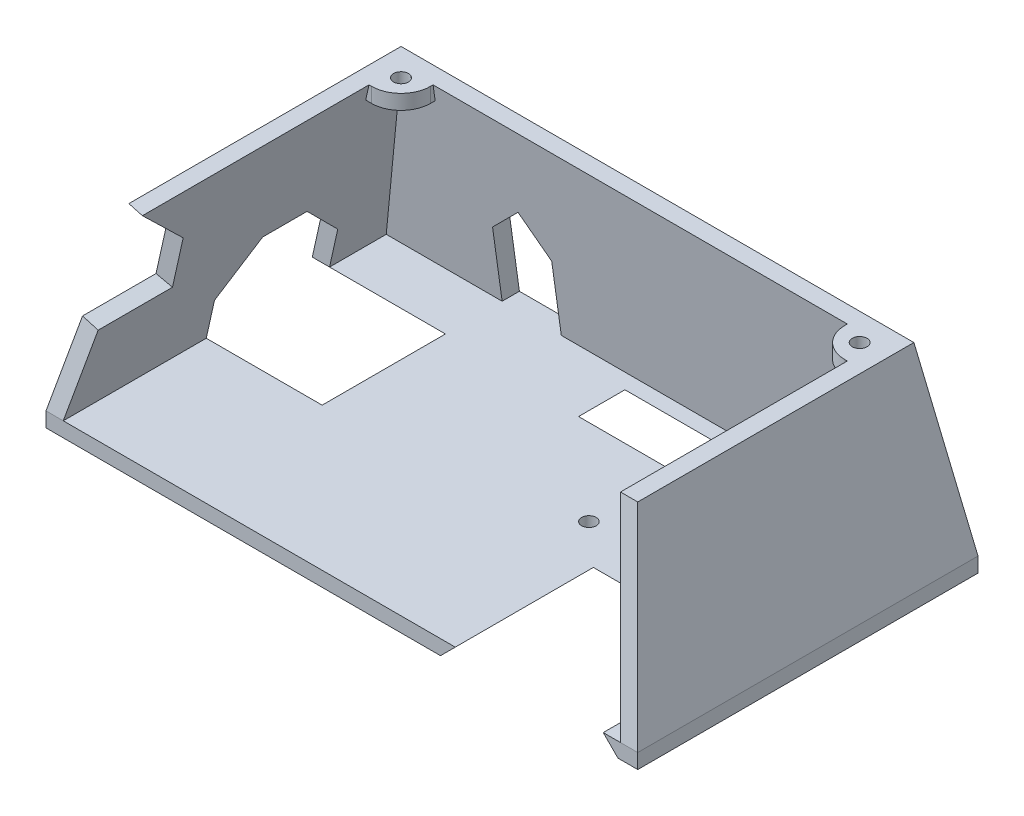
SolidWorks part; units mm, degrees
ref_plane "Front Plane" through (0, 0, 0) normal (0, 0, 1) x (1, 0, 0)
ref_plane "Top Plane" through (0, 0, 0) normal (0, 1, 0) x (1, 0, 0)
ref_plane "Right Plane" through (0, 0, 0) normal (1, 0, 0) x (0, 0, -1)
sketch "Sketch2" plane through (0, 0, 0) normal (0, 1, 0) x (1, 0, 0)
  line L0 (113, 0) -> (120, 0)
  line L1 (0, 0) -> (83, 0)
  line L2 (0, 0) -> (0, 69)
  line L3 (0, 69) -> (120, 69)
  line L4 (120, 0) -> (120, 69)
  line L5 (0, 0) -> (120, 69) construction
  line L6 (0, 69) -> (120, 0) construction
  line L7 (55, 62.4) -> (105, 62.4)
  line L8 (55, 62.4) -> (55, 53)
  line L9 (55, 53) -> (105, 53)
  line L10 (105, 62.4) -> (105, 53)
  line L11 (55, 62.4) -> (105, 53) construction
  line L12 (55, 53) -> (105, 62.4) construction
  line L13 (83, 28) -> (113, 28)
  line L14 (83, 28) -> (83, 0)
  line L16 (113, 28) -> (113, 0)
  line L17 (83, 28) -> (113, 0) construction
  line L18 (83, 0) -> (113, 28) construction
  point P18 (13.8909, 17.2356)
  dimension "D1" = 69
  dimension "D2" = 120
  dimension "D3" = 6.6
  dimension "D4" = 16
  dimension "D5" = 50
  dimension "D6" = 15
  dimension "D7" = 7
  dimension "D9" = 30
  dimension "D10" = 28
extrude "Boss-Extrude1" add sketch "Sketch2" along normal blind 3
sketch "Sketch3" plane through (0, 3, 0) normal (0, 1, 0) x (1, 0, 0)
  line L0 (3.5, 0) -> (3.5, 65.5)
  line L1 (3.5, 65.5) -> (116.5, 65.5)
  line L2 (116.5, 65.5) -> (116.5, 0)
  line L8 (0, 69) -> (0, 0)
  line L9 (0, 0) -> (83, 0)
  line L10 (83, 0) -> (83, 28)
  line L11 (83, 28) -> (113, 28)
  line L12 (113, 28) -> (113, 0)
  line L13 (113, 0) -> (120, 0)
  line L14 (120, 0) -> (120, 69)
  line L15 (120, 69) -> (0, 69)
  line L16 (0, 69) -> (0, 0)
  line L17 (0, 0) -> (3.5, 0)
  line L21 (116.5, 0) -> (120, 0)
  line L22 (120, 0) -> (120, 69)
  line L23 (120, 69) -> (0, 69)
  dimension "D2" = 3.5
  dimension "D3" = 3.5
  dimension "D4" = 3.5
  dimension "D1" = 0
ref_plane "Plane1" through (0, 39, 0) normal (0, 1, 0) x (1, 0, 0)
sketch "Sketch4" plane through (0, 39, 0) normal (0, 1, 0) x (1, 0, 0)
  line L0 (0, 73.6096) -> (8, 73.6096) construction
  line L1 (11.5, 8) -> (8, 8)
  line L2 (11.5, 8) -> (11.5, 60.5)
  line L4 (8, 8) -> (8, 64)
  line L5 (120, 32.6475) -> (112, 32.6475) construction
  line L6 (120, 0) -> (120, 69) construction
  line L7 (8, 64) -> (112, 64)
  line L11 (0, 69) -> (0, 0) construction
  line L14 (112, 64) -> (112, 8)
  line L15 (112, 8) -> (108.5, 8)
  line L17 (120, 69) -> (0, 69) construction
  line L22 (108.5, 60.5) -> (108.5, 8)
  line L27 (11.5, 60.5) -> (108.5, 60.5)
  point P4 (6.9167, 30.114)
  point P8 (54.6167, 56.9239)
  point P12 (99.6607, 30.8288)
  dimension "D1" = 3.5
  dimension "D2" = 3.5
  dimension "D3" = 3.5
  dimension "D4" = 56
  dimension "D5" = 104
  dimension "D6" = 5
loft "Loft1" add profiles "Sketch4", "Sketch3"
sketch "Sketch5" plane through (0, 39, 0) normal (0, 1, 0) x (1, 0, 0)
  line L0 (112, 64) -> (8, 64) construction
  line L1 (8, 64) -> (18, 64)
  line L2 (8, 64) -> (8, 54)
  line L3 (8, 54) -> (12, 54)
  line L4 (18, 64) -> (18, 60)
  line L5 (8, 64) -> (18, 54) construction
  line L6 (8, 54) -> (18, 64) construction
  line L7 (112, 64) -> (102, 64)
  line L8 (112, 64) -> (112, 54)
  line L9 (112, 54) -> (108, 54)
  line L10 (102, 64) -> (102, 60)
  line L11 (112, 64) -> (102, 54) construction
  line L12 (112, 54) -> (102, 64) construction
  line L13 (8, 64) -> (8, 8) construction
  line L14 (112, 8) -> (112, 64) construction
  arc A0 (108, 54) -> (102, 60) centre (108, 60) cw
  arc A1 (12, 54) -> (18, 60) centre (12, 60) ccw
  point P4 (0, 0)
  point P11 (0, 0)
  dimension "D5" = 6
  dimension "D1" = 10
  dimension "D2" = 10
  dimension "D3" = 10
  dimension "D4" = 10
extrude "Boss-Extrude2" add sketch "Sketch5" against normal blind 3
sketch "Sketch6" plane through (0, 39, 0) normal (0, 1, 0) x (1, 0, 0)
  line L0 (18, 64) -> (8, 64) construction
  line L1 (8, 64) -> (8, 54) construction
  line L2 (112, 54) -> (112, 64) construction
  line L3 (112, 64) -> (102, 64) construction
  circle A0 centre (13.5, 58.5) radius 1.5
  circle A1 centre (106.5, 58.5) radius 1.5
  dimension "D1" = 3
  dimension "D2" = 5.5
  dimension "D3" = 5.5
  dimension "D4" = 5.5
  dimension "D5" = 5.5
extrude "Cut-Extrude1" cut sketch "Sketch6" against normal up to next
sketch "Sketch7" plane through (0, 0, 0) normal (0, -1, 0) x (1, 0, 0)
  line L0 (120, -69) -> (0, -69) construction
  line L1 (-6, -29) -> (27, -29)
  line L2 (-6, -29) -> (-6, -54)
  line L3 (-6, -54) -> (27, -54)
  line L4 (27, -29) -> (27, -54)
  line L5 (-6, -29) -> (27, -54) construction
  line L6 (-6, -54) -> (27, -29) construction
  line L7 (0, -69) -> (0, 0) construction
  dimension "D1" = 15
  dimension "D2" = 33
  dimension "D3" = 25
  dimension "D4" = 27
extrude "Cut-Extrude2" cut sketch "Sketch7" against normal blind 18.5
chamfer "Chamfer1" distance 3 angle 45 4 edges at (55, 0, -57.7) (80, 0, -62.4) (105, 0, -57.7) (80, 0, -53)
sketch "Sketch8" plane through (0, 0, -69) normal (0, 0, -1) x (-1, 0, 0)
  line L0 (-120, 3) -> (0, 3) construction
  line L1 (-27, 3) -> (-39, 3)
  line L2 (-27, 3) -> (-27, 17.01)
  line L3 (-32.99, 23) -> (-33.01, 23)
  line L4 (-39, 3) -> (-39, 17.01)
  line L5 (-27, 3) -> (-39, 23) construction
  line L6 (-27, 23) -> (-39, 3) construction
  line L7 (-33.01, 23) -> (-39, 17.01)
  line L8 (36.0366, 39) -> (-36.0366, 39) construction
  line L9 (-27, 17.01) -> (-32.99, 23)
  point P4 (-24.5017, 30.8836)
  point P5 (0, 0)
  point P6 (0, 0)
  point P7 (-25.1522, 3.8279)
  point P8 (0, 0)
  point P9 (0, 0)
  point P12 (-28.8693, 15.086)
  point P13 (-20.1341, 29.118)
  point P15 (0, 0)
  point P16 (0, 0)
  point P17 (0, 0)
  point P18 (0, 0)
  point P19 (0, 0)
  point P20 (0, 0)
  point P23 (0, 0)
  point P24 (0, 0)
  dimension "D1" = 12
  dimension "D2" = 16
  dimension "D3" = 19
  dimension "D4" = 12
extrude "Cut-Extrude4" cut sketch "Sketch8" against normal up to next
chamfer "Chamfer2" distance 3 angle 45 3 edges at (83, 0, -14) (113, 0, -14) (98, 0, -28)
chamfer "Chamfer3" distance 3 angle 45 3 edges at (13.5, 0, -54) (27, 0, -41.5) (13.5, 0, -29)
sketch "Sketch9" plane through (0, 0, 0) normal (0, -1, 0) x (1, 0, 0)
  line L0 (89.5, -35.6) -> (74.5, -35.6) construction
  line L1 (120, 0) -> (120, -69) construction
  line L2 (120, -69) -> (0, -69) construction
  circle A0 centre (89.5, -35.6) radius 1.475
  circle A1 centre (74.5, -35.6) radius 1.475
  dimension "D1" = 2.95
  dimension "D2" = 15
  dimension "D3" = 30.5
  dimension "D4" = 33.4
extrude "Cut-Extrude5" cut sketch "Sketch9" against normal up to next
sketch "Sketch10" plane through (-0.6353, 0.1412, 0) normal (-0.9762, 0.2169, 0) x (0, 0, 1)
  line L0 (-0.7801, 20) -> (-18.6102, 20)
  line L1 (-18.6102, 20) -> (-18.6102, 30)
  line L2 (-18.6102, 30) -> (-7.7172, 40.893)
  line L3 (-0.7801, 20) -> (-7.7172, 40.893)
  line L4 (-26, 0) -> (0, 0) construction
  point P2 (8.1415, 10.5342)
  point P7 (0, 0)
  point P8 (0, 0)
  point P9 (-0.7801, 20)
  point P10 (0, 0)
  point P11 (0, 0)
  point P12 (0, 0)
  point P13 (-7.7172, 40.893)
  point P14 (0, 0)
  dimension "D1" = 135
  dimension "D2" = 20
  dimension "D3" = 10
extrude "Cut-Extrude6" cut sketch "Sketch10" against normal up to next
chamfer "Chamfer4" distance 8 angle 45 2 edges at (5.1944, 18.5, -29) (5.1944, 18.5, -54)
